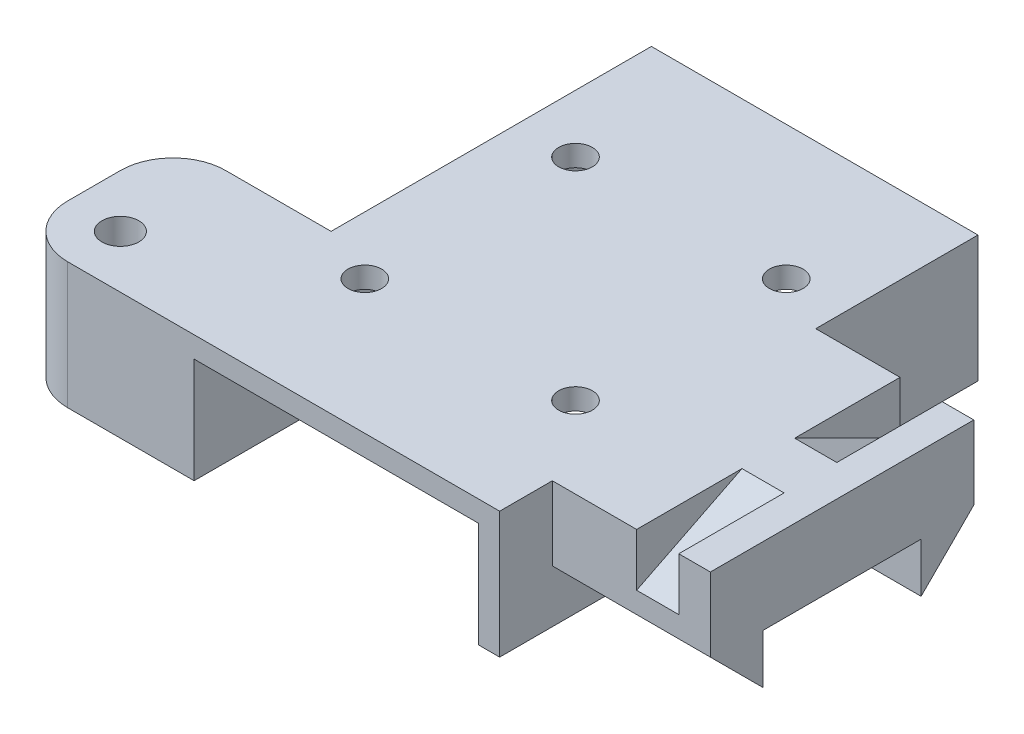
SolidWorks part; units mm, degrees
ref_plane "Front Plane" through (0, 0, 0) normal (0, 0, 1) x (1, 0, 0)
ref_plane "Top Plane" through (0, 0, 0) normal (0, 1, 0) x (1, 0, 0)
ref_plane "Right Plane" through (0, 0, 0) normal (1, 0, 0) x (0, 0, -1)
sketch "Sketch1" plane through (0, 0, 0) normal (0, 1, 0) x (1, 0, 0)
  line L1 (0, 0) -> (31, 0)
  line L2 (0, 0) -> (0, 45.4)
  line L3 (0, 45.4) -> (31, 45.4)
  line L4 (31, 0) -> (31, 45.4)
  dimension "D1" = 31
  dimension "D2" = 45.4
extrude "Boss-Extrude1" add sketch "Sketch1" along normal blind 12
sketch "Sketch2" plane through (0, 0, 0) normal (0, 0, 1) x (1, 0, 0)
  line L0 (0, 0) -> (31, 0) construction
  line L1 (2, 0) -> (29, 0)
  line L2 (2, 0) -> (2, 10)
  line L3 (2, 10) -> (29, 10)
  line L4 (29, 0) -> (29, 10)
  line L5 (0, 12) -> (0, 0) construction
  line L6 (31, 12) -> (31, 0) construction
  dimension "D1" = 2
  dimension "D2" = 2
  dimension "D3" = 10
extrude "Cut-Extrude1" cut sketch "Sketch2" against normal through all
sketch "Sketch3" plane through (0, 12, 0) normal (0, 1, 0) x (1, 0, 0)
  line L0 (15.5, 45.4) -> (15.5, 0) construction
  line L5 (5.5, 12.7) -> (25.5, 12.7) construction
  line L6 (5.5, 12.7) -> (5.5, 32.7) construction
  line L7 (5.5, 32.7) -> (25.5, 32.7) construction
  line L8 (25.5, 12.7) -> (25.5, 32.7) construction
  line L9 (5.5, 12.7) -> (25.5, 32.7) construction
  line L10 (5.5, 32.7) -> (25.5, 12.7) construction
  line L11 (31, 45.4) -> (0, 45.4) construction
  line L12 (0, 0) -> (31, 0) construction
  line L13 (0, 22.7) -> (31, 22.7) construction
  line L14 (0, 45.4) -> (0, 0) construction
  line L15 (31, 0) -> (31, 45.4) construction
  circle A0 centre (5.5, 32.7) radius 1.6
  circle A1 centre (25.5, 32.7) radius 1.6
  circle A2 centre (25.5, 12.7) radius 1.6
  circle A3 centre (5.5, 12.7) radius 1.6
  point P0 (15.5, 22.7)
  dimension "D3" = 3.2
  dimension "D1" = 20
  dimension "D2" = 20
extrude "Cut-Extrude2" cut sketch "Sketch3" against normal blind 10
sketch "Sketch4" plane through (0, 0, 0) normal (-1, 0, 0) x (0, 0, 1)
  line L0 (-45.4, 12) -> (0, 12) construction
  line L1 (-15, 12) -> (0, 12)
  line L2 (-15, 12) -> (-15, 0)
  line L3 (-15, 0) -> (0, 0)
  line L4 (0, 12) -> (0, 0)
  dimension "D1" = 15
extrude "Boss-Extrude2" add sketch "Sketch4" along normal blind 15
sketch "Sketch5" plane through (0, 12, 0) normal (0, 1, 0) x (1, 0, 0)
  line L2 (-15, 0) -> (31, 0) construction
  line L3 (0, 45.4) -> (0, 15) construction
  circle A0 centre (-10, 5) radius 1.75
  dimension "D1" = 3.5
  dimension "D2" = 5
  dimension "D3" = 10
extrude "Cut-Extrude3" cut sketch "Sketch5" against normal blind 20
fillet "Fillet1" radius 5 2 edges at (-15, 6, -15) (-15, 6, 0)
sketch "Sketch6" plane through (31, 0, 0) normal (1, 0, 0) x (0, 0, -1)
  line L9 (5, 0) -> (10, 0)
  line L10 (0, 0) -> (45.4, 0) construction
  line L11 (10, 0) -> (10, 4.7)
  line L12 (10, 4.7) -> (25, 4.7)
  line L13 (25, 4.7) -> (25, 0)
  line L14 (25, 0) -> (30, 0)
  line L15 (30, 0) -> (30, 12)
  line L16 (30, 12) -> (5, 12)
  line L17 (5, 12) -> (5, 0)
  line L18 (0, 12) -> (45.4, 12) construction
  line L19 (0, 12) -> (0, 0) construction
  dimension "D1" = 5
  dimension "D2" = 5
  dimension "D3" = 4.7
  dimension "D4" = 15
  dimension "D5" = 5
extrude "Boss-Extrude3" add sketch "Sketch6" along normal blind 15
chamfer "Chamfer1" distance 5 angle 45 2 edges at (38.5, 0, -5) (38.5, 0, -30)
ref_plane "Plane1" through (43, 0, 0) normal (1, 0, 0) x (0, 0, -1)
sketch "Sketch7" plane through (43, 0, 0) normal (1, 0, 0) x (0, 0, -1)
  line L0 (5, 7) -> (15, 12)
  line L1 (5, 12) -> (5, 5) construction
  line L3 (15, 12) -> (5, 12)
  line L4 (5, 12) -> (5, 7)
  line L5 (30, 7) -> (20, 12)
  line L6 (30, 5) -> (30, 12) construction
  line L7 (20, 12) -> (30, 12)
  line L8 (30, 12) -> (30, 7)
  line L9 (30, 12) -> (5, 12) construction
  dimension "D1" = 5
  dimension "D2" = 5
  dimension "D3" = 10
  dimension "D4" = 10
extrude "Cut-Extrude4" cut sketch "Sketch7" against normal blind 4
mirror "Mirror1" [suppressed] of bodies 111 105
delete or keep bodies "Body-Delete/Keep 1" [suppressed] type delete bodies bodies 111
mirror "Mirror2" [suppressed] of bodies 105
mirror "Mirror3" [suppressed] of bodies 107
delete or keep bodies "Body-Delete/Keep 2" [suppressed] type delete bodies bodies 105 107
mirror "Mirror4" [suppressed] of bodies 111 105
delete or keep bodies "Body-Delete/Keep 3" [suppressed] type delete bodies bodies 111
sketch "Sketch10" [suppressed] plane through (46, 0, 0) normal (1, 0, 0) x (0, 0, -1)
  line L0 (60.8, 12) -> (85.8, 12) construction
  line L1 (80.8, 12) -> (85.8, 12)
  line L2 (80.8, 12) -> (80.8, -14.5)
  line L3 (80.8, -14.5) -> (85.8, -14.5)
  line L4 (85.8, 12) -> (85.8, -14.5)
  line L5 (80.8, 0) -> (80.8, 4.7) construction
  line L6 (85.8, 12) -> (85.8, 5) construction
  dimension "D1" = 26.5
extrude "Boss-Extrude7" [suppressed] add sketch "Sketch10" along normal blind 2
sketch "Sketch11" [suppressed] plane through (46, 0, 0) normal (-1, 0, 0) x (0, 0, 1)
  line L0 (-80.8, 0) -> (-80.8, -14.5) construction
  line L1 (-85.8, -14.5) -> (-80.8, -14.5)
  line L2 (-85.8, -14.5) -> (-85.8, -13)
  line L3 (-85.8, -13) -> (-80.8, -13)
  line L4 (-80.8, -14.5) -> (-80.8, -13)
  dimension "D1" = 1.5
extrude "Boss-Extrude8" [suppressed] add sketch "Sketch11" along normal blind 10
fillet "Fillet2" [suppressed] radius 7.5
